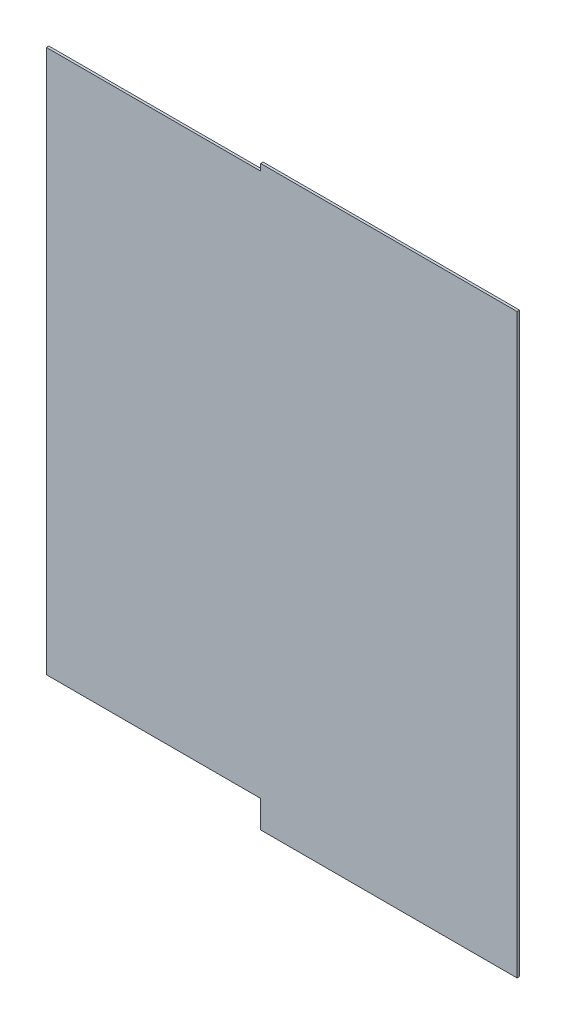
SolidWorks part; units mm, degrees
ref_plane "Спереди" through (0, 0, 0) normal (0, 0, 1) x (1, 0, 0)
ref_plane "Сверху" through (0, 0, 0) normal (0, 1, 0) x (1, 0, 0)
ref_plane "Справа" through (0, 0, 0) normal (1, 0, 0) x (0, 0, -1)
sketch "Эскиз1" plane through (0, 0, 0) normal (0, 0, 1) x (1, 0, 0)
  line L0 (0, -883) -> (518, -883)
  line L1 (1138.3, -949) -> (518, -949)
  line L2 (0, -883) -> (0, 431)
  line L3 (0, 431) -> (518, 431)
  line L4 (518, 431) -> (518, 447)
  line L5 (518, 447) -> (1138.3, 447)
  line L6 (1138.3, 447) -> (518, 447) construction
  line L7 (1138.3, 441) -> (1138.3, 447) construction
  line L8 (1138.3, 447) -> (1138.3, -949)
  line L9 (518, 447) -> (518, -949) construction
  line L10 (0, -883) -> (524, -883) construction
  line L11 (518, -883) -> (518, -949)
  point P0 (0, -883)
extrude "Бобышка-Вытянуть1" add sketch "Эскиз1" against normal blind 6
equation "\"Ширина груза\"= 420"
equation "\"Глубина груза\"= 490"
equation "\"Высота груза\"= 297"
equation "\"Ширина ячейки\"= \"Ширина груза\" + 10"
equation "\"Глубина ячейки\"= \"Глубина груза\" + 10"
equation "\"Высота ячейки\"= \"Высота груза\" + 10 + 13"
equation "\"Колво ячеек ширина\"= 2"
equation "\"Колво ячеек высота\"= 2"
equation "\"Толщина стенки\" = 6"
equation "\"Крепление дверцы\"= 5"
equation "\"Ширина рейки\"= \"Толщина шестерни\""
equation "\"Высота рейки\"= 20"
equation "\"Высота пола\"= 20"
equation "\"Колво полозьев\"= 5"
equation "\"Отступ рейки\"= 20"
equation "\"Глубина каретки\"= \"Глубина ячейки\" + 30 + \"Мотор Y высота корпуса\" + 20"
equation "\"Длинна рейки\"= ( \"Ширина ячейки\" + \"Толщина стенки\" + \"Крепление дверцы\" ) * \"Колво ячеек ширина\" + \"Ширина ячейки выгрузки\" * \"Колво выгрузки\" + \"Толщина стенки\""
equation "\"Отступ шпильки\"= 26"
equation "\"Диаметр шпильки\"= 5"
equation "\"Длинна шпильки\"= ( \"Высота ячейки\" + \"Толщина стенки\" + \"Высота пола\" ) * \"Колво ячеек высота\" + ( \"Толщина стенки\" + \"Отступ рейки\" ) * 2 "
equation "\"Ширина пластины\"= 50  "
equation "\"Высота зона выгрузки\"= \"Высота ячейки\" * 2 + \"Толщина стенки\" * 2"
equation "\"Колво выгрузки\"= 1"
equation "\"Ширина ячейки выгрузки\"= \"Ширина ячейки\" + \"Толщина стенки\" + \"Отступ крепления мотора фиксации\"*2"
equation "\"Отступ крепления мотора фиксации\" = 30"
equation "\"Мотор X ширина корпуса\"= 42.3"
equation "\"Мотор X высота корпуса\"= 42.3"
equation "\"Мотор X длина корпуса\"= 40"
equation "\"Мотор X вылет вала\"= 19.8"
equation "\"Мотор Y ширина корпуса\"= 42.3"
equation "\"Мотор Y высота корпуса\"= 42.3"
equation "\"Мотор Y длина корпуса\"= 48"
equation "\"Мотор Y вылет вала\"= 30"
equation "\"Мотор Z ширина корпуса\"= 42"
equation "\"Мотор Z высота корпуса\"= 42"
equation "\"Мотор Z длина корпуса\"= 40"
equation "\"Мотор Z вылет вала\"= 23"
equation "\"Мотор диаметр вала ПРЕДВ\"= 5"
equation "\"Мотор шаг крепления ПРЕДВ\"= 31"
equation "\"Мотор диаметр отверстий ПРЕДВ\"= 3"
equation "\"Мотор глубина отверстий ПРЕДВ\"= 4.5"
equation "\"Мотор диаметр буртика ПРЕДВ\"= 22"
equation "\"Мотор высота буртика ПРЕДВ\"= 2"
equation "\"Мотор диаметр шкива ПРЕДВ\"= 16"
equation "\"Мотор длина шкива ПРЕДВ\"= 12"
equation "\"Мотор отступ шкива ПРЕДВ\"= 5"
equation "\"Мотор X шаг градусов\"= 1.8"
equation "\"Мотор Y шаг градусов\"= 1.8"
equation "\"Мотор Z шаг градусов\"= 1.8"
equation "\"Мотор Y диаметр ротора\"= 25.78"
equation "\"Толщина шестерни\"= 10"
equation "\"D1@Бобышка-Вытянуть1\"=\"Толщина стенки\""
